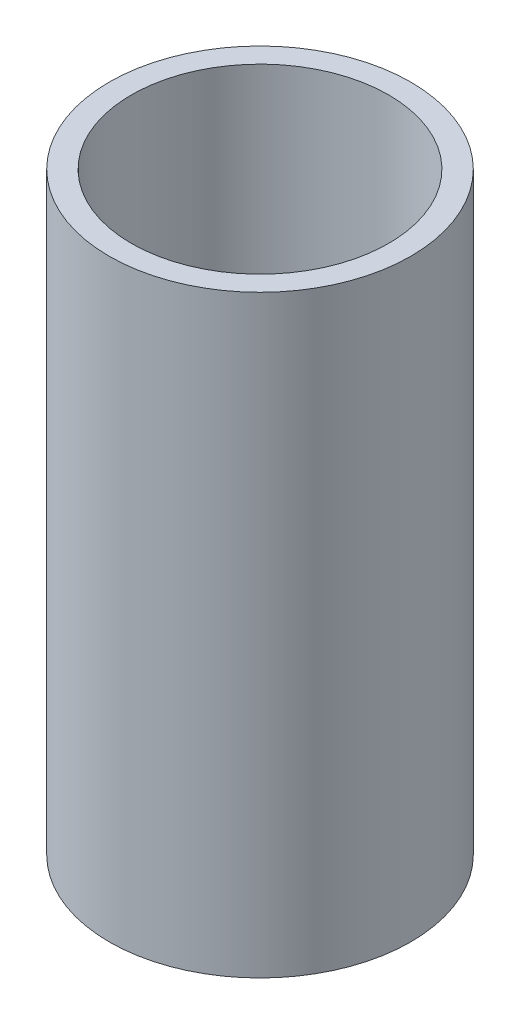
SolidWorks part; units mm, degrees
material "AISI 4130 Steel, annealed at 865C"
ref_plane "Front Plane" through (0, 0, 0) normal (0, 0, 1) x (1, 0, 0)
ref_plane "Top Plane" through (0, 0, 0) normal (0, 1, 0) x (1, 0, 0)
ref_plane "Right Plane" through (0, 0, 0) normal (1, 0, 0) x (0, 0, -1)
sketch "Sketch1" plane through (0, 0, 0) normal (0, 1, 0) x (1, 0, 0)
  circle A0 centre (0, 0) radius 13
  circle A1 centre (0, 0) radius 15.24
  circle A2 centre (0, 0) radius 15.24 construction
  dimension "D1" = 26
extrude "Boss-Extrude1" add sketch "Sketch1" along normal blind 60
